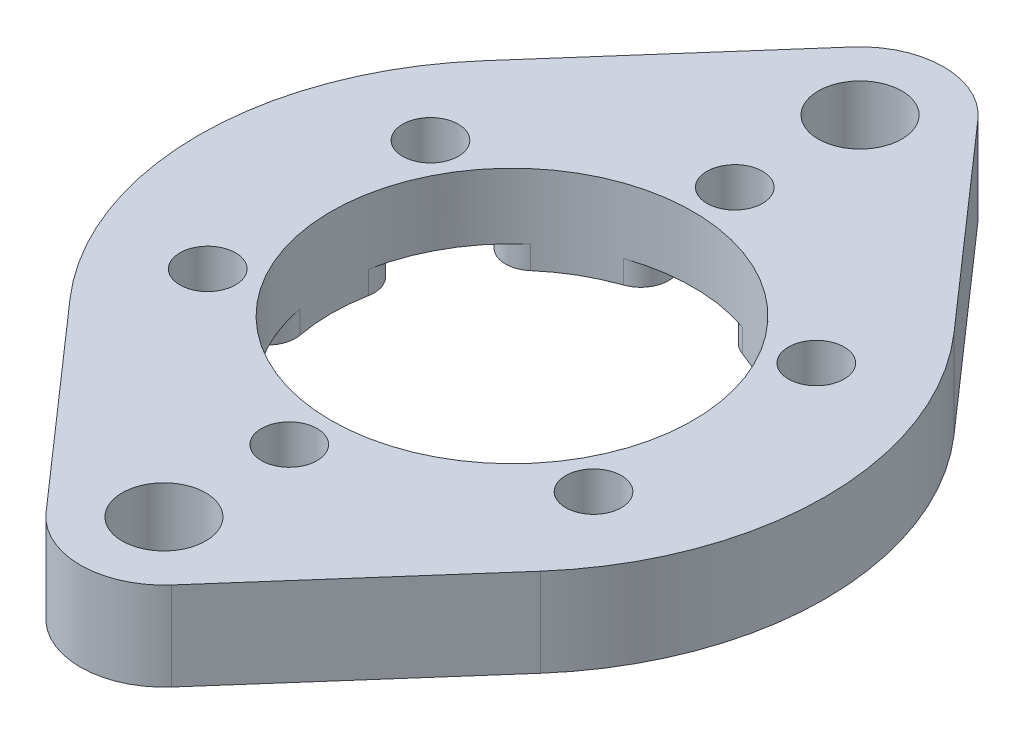
SolidWorks part; units mm, degrees
ref_plane "Front Plane" through (0, 0, 0) normal (0, 0, 1) x (1, 0, 0)
ref_plane "Top Plane" through (0, 0, 0) normal (0, 1, 0) x (1, 0, 0)
ref_plane "Right Plane" through (0, 0, 0) normal (1, 0, 0) x (0, 0, -1)
ref_axis "Axis1" through (0, -54.0054, 0) along (0, 1, 0)
sketch "Sketch1" plane through (0, 0, 0) normal (0, 1, 0) x (1, 0, 0)
  line L0 (0, 13) -> (0, 19) construction
  line L1 (-4.5076, 28.96) -> (-16.9035, 14.85)
  line L3 (-13, 0) -> (13, 0) construction
  line L5 (-4.5076, -28.96) -> (-16.9035, -14.85)
  line L8 (4.5076, 28.96) -> (16.9035, 14.85)
  line L9 (4.5076, -28.96) -> (16.9035, -14.85)
  circle A0 centre (0, 0) radius 13
  circle A1 centre (0, 0) radius 19 construction
  circle A2 centre (0, 16) radius 2
  circle A3 centre (13.8564, 8) radius 2
  circle A4 centre (13.8564, -8) radius 2
  circle A5 centre (0, -16) radius 2
  circle A6 centre (-13.8564, -8) radius 2
  circle A7 centre (-13.8564, 8) radius 2
  circle A8 centre (0, 0) radius 25 construction
  circle A9 centre (0, 25) radius 3
  circle A10 centre (0, -25) radius 3
  arc A11 (4.5076, 28.96) -> (-4.5076, 28.96) centre (0, 25) ccw
  arc A13 (4.5076, -28.96) -> (-4.5076, -28.96) centre (0, -25) cw
  arc A14 (-16.9035, 14.85) -> (-16.9035, -14.85) centre (0, 0) ccw
  arc A15 (16.9035, -14.85) -> (16.9035, 14.85) centre (0, 0) ccw
  point P21 (0, 0)
  point P27 (0, 0)
  point P30 (7.5, 75.1813)
  dimension "D1" = 38
  dimension "D2" = 26
  dimension "D3" = 4
  dimension "D5" = 50
  dimension "D6" = 6
  dimension "D8" = 22.5
  dimension "D9" = 3
  dimension "D4" = 6
  dimension "D7" = 2
extrude "Boss-Extrude1" add sketch "Sketch1" along normal blind 6.35
sketch "Sketch2" plane through (0, 6.35, 0) normal (0, 1, 0) x (1, 0, 0)
  circle A0 centre (0, 0) radius 19 construction
  circle A1 centre (0, 0) radius 19
extrude "Cut-Extrude1" [suppressed] cut sketch "Sketch2" against normal blind 3.175
ref_plane "Plane1" through (0, 1.65, 0) normal (0, 1, 0) x (1, 0, 0)
sketch "Sketch3" plane through (0, 0, 0) normal (0, -1, 0) x (1, 0, 0)
  circle A0 centre (0, -16) radius 3.25
  circle A1 centre (-13.8564, -8) radius 3.25
  circle A2 centre (-13.8564, 8) radius 3.25
  circle A3 centre (0, 16) radius 3.25
  circle A4 centre (13.8564, 8) radius 3.25
  circle A5 centre (13.8564, -8) radius 3.25
  point P3 (11.5782, 46.0227)
  point P4 (0, 0)
  point P16 (0, 0)
  dimension "D2" = 6.5
  dimension "D1" = 6
extrude "Cut-Extrude2" cut sketch "Sketch3" against normal up to surface (1.65 mm away) up to plane "Plane1"
fillet "Fillet1" radius 2 12 edges at (1.1257, 0.825, -12.9512) (-1.1257, 0.825, -12.9512) (-10.6532, 0.825, -7.4505) (-11.7789, 0.825, -5.5007) (-11.7789, 0.825, 5.5007) (-10.6532, 0.825, 7.4505) (-1.1257, 0.825, 12.9512) (1.1257, 0.825, 12.9512) (10.6532, 0.825, 7.4505) (11.7789, 0.825, 5.5007) (10.6532, 0.825, -7.4505) (11.7789, 0.825, -5.5007)
